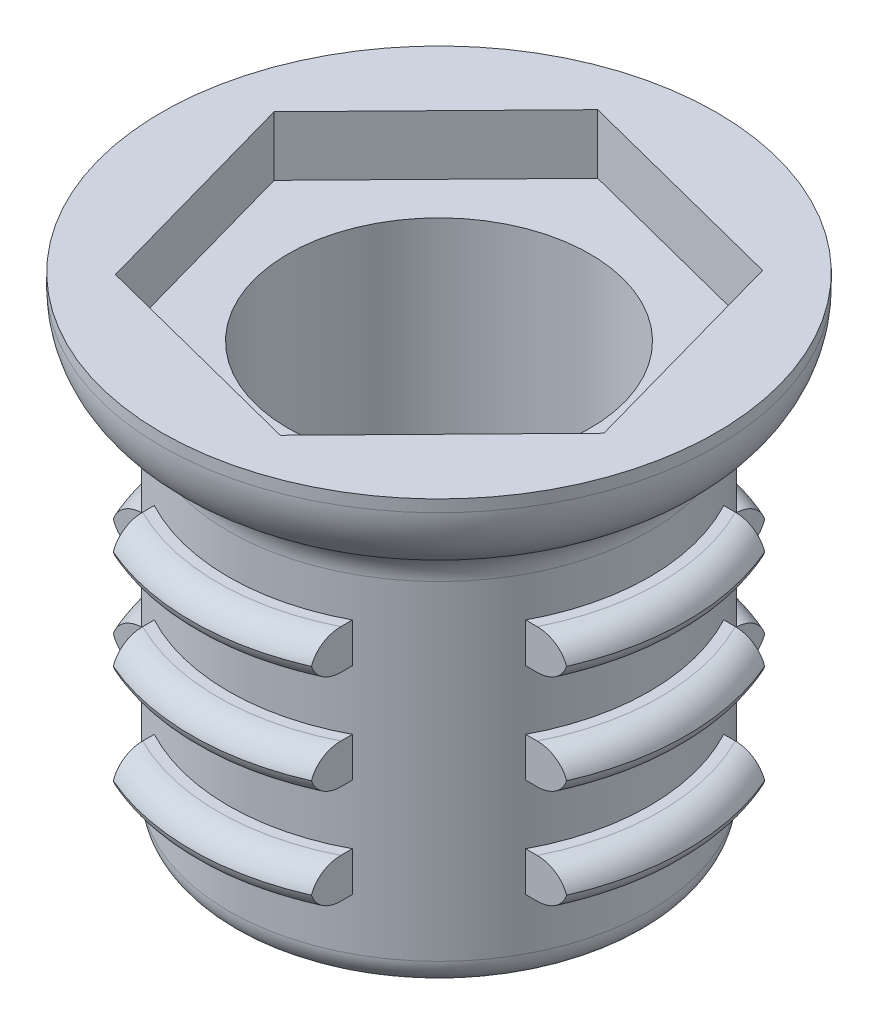
SolidWorks part; units mm, degrees
ref_plane "Plano frontal" through (0, 0, 0) normal (0, 0, 1) x (1, 0, 0)
ref_plane "Plano superior" through (0, 0, 0) normal (0, 1, 0) x (1, 0, 0)
ref_plane "Plano direito" through (0, 0, 0) normal (1, 0, 0) x (0, 0, -1)
sketch "Esboço1" plane through (0, 0, 0) normal (0, 1, 0) x (1, 0, 0)
  circle A0 centre (0, 0) radius 3.81
  dimension "D1" = 7.62
extrude "Extrusão-Fina1" add sketch "Esboço1" along normal blind 10 thin thin type one direction wall 1.5
sketch "Esboço2" plane through (0, 10, 0) normal (0, 1, 0) x (1, 0, 0)
  circle A0 centre (0, 0) radius 7
  circle A1 centre (0, 0) radius 3.81
  dimension "D1" = 14
extrude "Ressalto-extrusão1" add sketch "Esboço2" along normal blind 2
sketch "Esboço3" plane through (0, 12, 0) normal (0, 1, 0) x (1, 0, 0)
  line L1 (4.0372, 4.1272) -> (-1.5557, 5.56)
  line L2 (-1.5557, 5.56) -> (-5.5929, 1.4327)
  line L3 (-5.5929, 1.4327) -> (-4.0372, -4.1272)
  line L4 (-4.0372, -4.1272) -> (1.5557, -5.56)
  line L5 (1.5557, -5.56) -> (5.5929, -1.4327)
  line L6 (5.5929, -1.4327) -> (4.0372, 4.1272)
  circle A0 centre (0, 0) radius 5 construction
  dimension "D1" = 10
extrude "Corte-extrusão1" cut sketch "Esboço3" against normal blind 1.5
ref_plane "Plano1" through (0, 2, 0) normal (0, -1, 0) x (-1, 0, 0)
sketch "Esboço4" plane through (0, 2, 0) normal (0, -1, 0) x (-1, 0, 0)
  line L0 (5.75, -2.5) -> (5.75, 2.5) construction
  line L1 (5.75, 2.5) -> (2.5, 2.5)
  line L2 (2.5, 2.5) -> (2.5, 5.75)
  line L3 (2.5, 5.75) -> (-2.5, 5.75) construction
  line L4 (-2.5, 5.75) -> (-2.5, 2.5)
  line L5 (-2.5, 2.5) -> (-5.75, 2.5)
  line L6 (-5.75, 2.5) -> (-5.75, -2.5) construction
  line L7 (-5.75, -2.5) -> (-2.5, -2.5)
  line L8 (-2.5, -2.5) -> (-2.5, -5.75)
  line L9 (-2.5, -5.75) -> (2.5, -5.75) construction
  line L10 (2.5, -5.75) -> (2.5, -2.5)
  line L11 (2.5, -2.5) -> (5.75, -2.5)
  line L12 (0, -1.513) -> (0, 1.6692) construction
  arc A0 (5.75, -2.5) -> (5.75, 2.5) centre (0, 0) ccw
  arc A1 (-2.5, -5.75) -> (2.5, -5.75) centre (0, 0) ccw
  arc A2 (-5.75, 2.5) -> (-5.75, -2.5) centre (0, 0) ccw
  arc A3 (2.5, 5.75) -> (-2.5, 5.75) centre (0, 0) ccw
  point P3 (0, 5.75)
  point P13 (0, -5.75)
  point P15 (5.75, 0)
  point P16 (-5.75, 0)
  dimension "D1" = 5
  dimension "D2" = 5
  dimension "D4" = 11.5
extrude "Ressalto-extrusão2" add sketch "Esboço4" against normal blind 1
fillet "Filete1" radius 0.7 8 edges at (6.27, 2, 0) (6.27, 3, 0) (0, 2, -6.27) (0, 3, -6.27) (-6.27, 2, 0) (-6.27, 3, 0) (0, 2, 6.27) (0, 3, 6.27)
pattern_linear "Padrão linear2" count 3 spacing 2.5 along (0, 1, 0) of "Filete1", "Ressalto-extrusão2"
fillet "Filete2" radius 0.7 1 edges at (5.31, 0, 0)
fillet "Filete3" radius 1 1 edges at (5.31, 10, 0)
fillet "Filete4" radius 2 1 edges at (0, 10, 7)
extrude "Corte-extrusão2" cut sketch "Esboço1<2>" along normal through all
sketch "Esboço1<2>" plane through (0, 0, 0) normal (0, 1, 0) x (1, 0, 0) same geometry as "Esboço1"
